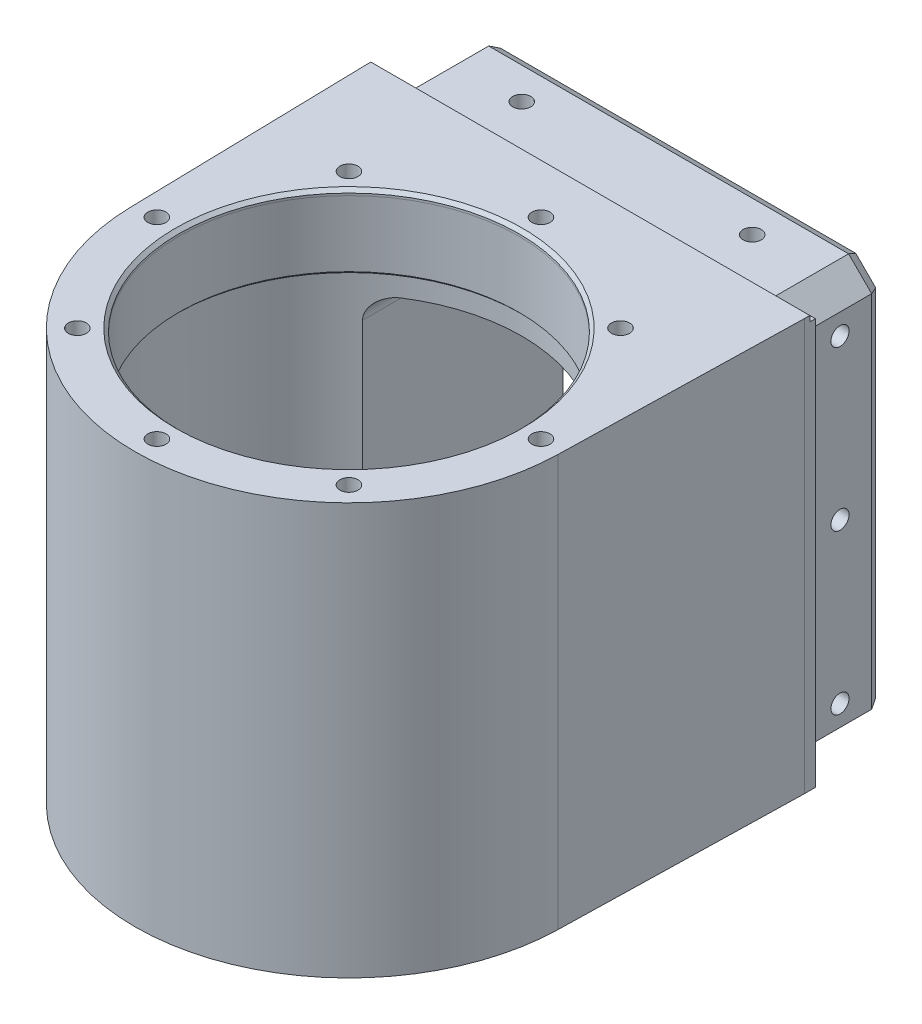
SolidWorks part; units mm, degrees
material "3.3547 (EN-AW 5083)"
ref_plane "Front Plane" through (0, 0, 0) normal (0, 0, 1) x (1, 0, 0)
ref_plane "Top Plane" through (0, 0, 0) normal (0, 1, 0) x (1, 0, 0)
ref_plane "Right Plane" through (0, 0, 0) normal (1, 0, 0) x (0, 0, -1)
ref_axis "Elbow" through (0, -41, 45) along (0, 1, 0)
sketch "Sketch1" plane through (0, 0, 0) normal (1, 0, 0) x (0, 0, -1)
  line L0 (-14, 37) -> (-76, 37) construction
  line L1 (-14, 25) -> (-76, 25) construction
  line L2 (-14, 37) -> (-76, 37) construction
  line L3 (-14, -34) -> (-16, -34)
  line L5 (-76, -34) -> (-14, -34) construction
  line L6 (-76, -34) -> (-14, -34) construction
  line L7 (-16, -34) -> (-16, -37)
  line L8 (-16, -37) -> (-6, -37)
  line L9 (-6, -37) -> (-6, 38)
  line L10 (-6, 38) -> (-14, 38)
  line L11 (-45, 37) -> (-45, -49.5069) construction
  line L12 (-76, -22) -> (-14, -22) construction
  line L13 (-76, -22) -> (-14, -22) construction
  line L14 (-14, 25) -> (-76, 25) construction
  line L15 (-14, 38) -> (-14, 25)
  line L16 (-14, 25) -> (-13.5, 25)
  line L17 (-13.5, 25) -> (-13.5, -22)
  line L18 (-13.5, -22) -> (-14, -22)
  line L19 (-14, -22) -> (-14, -34)
  dimension "D1" = 3
  dimension "D2" = 8
  dimension "D3" = 1
  dimension "D4" = 2
  dimension "D5" = 0.5
revolve "Revolve1" add sketch "Sketch1" angle 360 about axis through (0, -41, 45) along (0, 1, 0)
sketch "Sketch2" plane through (0, 0, 0) normal (1, 0, 0) x (0, 0, -1)
  line L0 (-14, 37) -> (-76, 37) construction
  line L1 (-14, 37) -> (-76, 37) construction
  line L2 (-14, 37) -> (-16, 37)
  line L3 (-16, 37) -> (-16, 41.5)
  line L4 (-16, 41.5) -> (-6, 41.5)
  line L5 (-6, 41.5) -> (-6, 38.5)
  line L6 (-6, 38.5) -> (-14, 38.5)
  line L7 (-14, 38.5) -> (-14, 37)
  line L9 (-45, 37) -> (-45, 58.1094) construction
  line L10 (-6, -37) -> (-6, 38) construction
  line L11 (-6, 38) -> (-84, 38) construction
  dimension "D1" = 2
  dimension "D2" = 3
  dimension "D3" = 0.5
revolve "Revolve2" add sketch "Sketch2" angle 360 about axis through (0, -41, 45) along (0, 1, 0)
sketch "Sketch3" plane through (0, 0, 0) normal (0, 1, 0) x (1, 0, 0)
  line L0 (0, -41.25) -> (0, 41.25) construction
  line L2 (-40, -2) -> (-38.9897, -45.8974)
  line L4 (40, 0) -> (-40, 0) construction
  line L5 (40, 0) -> (-40, 0) construction
  line L6 (40, -2) -> (38.9897, -45.8974)
  line L7 (-40, -2) -> (-40, 0)
  line L8 (40, -2) -> (40, 0)
  line L9 (-40, 0) -> (40, 0)
  circle A0 centre (0, -45) radius 39 construction
  arc A1 (-38.9897, -45.8974) -> (38.9897, -45.8974) centre (0, -45) cw
  point P15 (0, 0)
  dimension "D1" = 2
extrude "Boss-Extrude1" add sketch "Sketch3" along normal up to surface and the other way up to surface contours L2 A1 L6 L8 L9 L7 up to face at (0, 38, 14) other way up to face at (0, -37, 6)
sketch "Sketch4" plane through (0, 0, 0) normal (0, 0, -1) x (-1, 0, 0)
  line L0 (-37, 37) -> (37, 37) construction
  line L1 (-37, 37) -> (37, 37) construction
  line L3 (-37, -37) -> (37, -37)
  line L4 (-37, -37) -> (-37, 37)
  line L5 (-37, 37) -> (37, 37)
  line L6 (37, -37) -> (37, 37)
  line L7 (-37, -37) -> (37, 37) construction
  line L8 (-37, 37) -> (37, -37) construction
  point P2 (0, 0)
extrude "Boss-Extrude2" add sketch "Sketch4" along normal blind 15
sketch "Sketch5" plane through (0, 38, 0) normal (0, 1, 0) x (1, 0, 0)
  line L0 (0, 0) -> (0, -62.5046) construction
  line L1 (-40, 0) -> (40, 0) construction
  line L2 (-29.8132, -10) -> (-29.8132, 0) construction
  line L3 (-29.8132, -10) -> (-39.8106, -10.2301) construction
  line L4 (-40, -2) -> (-38.9897, -45.8974) construction
  circle A1 centre (-29.8132, -10) radius 6
  circle A2 centre (29.8132, -10) radius 6
  dimension "D2" = 12
  dimension "D1" = 10
extrude "Cut-Extrude1" [suppressed] cut sketch "Sketch5" against normal through all
sketch "Sketch12" plane through (0, 41.5, 0) normal (0, 1, 0) x (1, 0, 0)
  line L0 (0, -14) -> (0, -6) construction
  line L1 (0, -45) -> (0, -10) construction
  line L2 (0, -45) -> (24.7487, -20.2513) construction
  circle A2 centre (0, -45) radius 39
  circle A3 centre (0, -45) radius 31 construction
  circle A4 centre (0, -45) radius 39 construction
  circle A6 centre (0, -45) radius 31 construction
  point P11 (0, -10)
  point P20 (24.7487, -20.2513)
  point P21 (35, -45)
  point P22 (24.7487, -69.7487)
  point P23 (0, -80)
  point P24 (-24.7487, -69.7487)
  point P25 (-35, -45)
  point P26 (-24.7487, -20.2513)
  dimension "D1" = 8
  dimension "D2" = 45
hole_wizard "M4 Clearance Hole1" positions "Sketch12" profile "Sketch11" hole size "M4" standard "DIN" end condition up to next
sketch "Sketch11" plane through (-24.7487, 41.5, 20.2513) normal (1, 0, 0) x (0, 0, 1)
  line L0 (0, 0) -> (0, 3)
  line L1 (0, 3) -> (2.15, 3)
  line L2 (2.15, 3) -> (2.15, 0)
  line L5 (2.15, 0) -> (0, 0)
  line L11 (0, -6.35) -> (0, 107.95) construction
  dimension "Thru Hole Dia." = 4.3
  dimension "Thru Hole Depth" = 3
sketch "Sketch17" plane through (0, 38, 0) normal (0, 1, 0) x (1, 0, 0)
  point P0 (0, -10)
  point P3 (24.7487, -20.2513)
  point P6 (35, -45)
  point P9 (-24.7487, -20.2513)
  point P12 (-35, -45)
  point P15 (-24.7487, -69.7487)
  point P18 (0, -80)
  point P21 (24.7487, -69.7487)
hole_wizard "M4 Tapped Hole1" positions "Sketch17" profile "Sketch16" tap size "M4" standard "DIN"
sketch "Sketch16" plane through (0, 38, 10) normal (1, 0, 0) x (0, 0, 1)
  line L0 (0, 0) -> (0, 12.4914)
  line L1 (0, 12.4914) -> (1.65, 11.5)
  line L2 (1.65, 11.5) -> (1.65, 0)
  line L5 (1.65, 0) -> (0, 0)
  line L10 (0, 12.4914) -> (-1.65, 11.5) construction
  line L11 (0, -6.35) -> (0, 107.95) construction
  dimension "Tap Drill Dia." = 3.3
  dimension "Tap Drill Depth" = 11.5
  dimension "Drill Angle" = 118
cosmetic thread "Hole Thread25" parameters "D1"=8, "D2"=4
cosmetic thread "Hole Thread26" parameters "D1"=8, "D2"=4
cosmetic thread "Hole Thread27" parameters "D1"=8, "D2"=4
cosmetic thread "Hole Thread28" parameters "D1"=8, "D2"=4
cosmetic thread "Hole Thread29" parameters "D1"=8, "D2"=4
cosmetic thread "Hole Thread30" parameters "D1"=8, "D2"=4
cosmetic thread "Hole Thread31" parameters "D1"=8, "D2"=4
cosmetic thread "Hole Thread32" parameters "D1"=8, "D2"=4
sketch "Sketch18" plane through (0, 0, 0) normal (1, 0, 0) x (0, 0, -1)
  line L0 (0, 0) -> (-96.5587, 0) construction
  line L1 (-84, 25) -> (-76, 25)
  line L2 (-84, 38) -> (-84, -37) construction
  line L3 (-70.3666, 23.2623) -> (-48.3666, 8.2623)
  line L4 (-84, 25) -> (-84, -22)
  line L5 (-65.9666, -20.2623) -> (-48.3666, -8.2623)
  line L6 (-84, -22) -> (-71.6, -22)
  line L7 (-45.8974, 38) -> (-84, 38) construction
  line L8 (-84, -37) -> (-45.8974, -37) construction
  arc A0 (-65.9666, -20.2623) -> (-71.6, -22) centre (-71.6, -12) cw
  arc A1 (-48.3666, 8.2623) -> (-48.3666, -8.2623) centre (-54, 0) cw
  arc A2 (-76, 25) -> (-70.3666, 23.2623) centre (-76, 15) cw
  point P10 (-77, 0)
  point P13 (-68.5153, -22)
  point P16 (-36.2486, 0)
  point P19 (-72.9153, 25)
  point P22 (-77.8, -22)
  dimension "D1" = 10
  dimension "D2" = 13
  dimension "D3" = 30
  dimension "D4" = 8
  dimension "D5" = 15
  dimension "D6" = 12.4
extrude "Cut-Extrude2" [suppressed] cut sketch "Sketch18" against normal through all both and the other way through all
sketch "Sketch19" plane through (0, 0, 0) normal (0, 0, -1) x (-1, 0, 0)
  line L1 (40, -37) -> (37, -37)
  line L2 (40, -37) -> (40, 38)
  line L6 (37, 37) -> (-37, 37) construction
  line L7 (37, 37) -> (-37, 37)
  line L8 (37, -37) -> (37, 37) construction
  line L9 (37, -37) -> (37, 37)
  line L11 (40, 38) -> (-40, 38) construction
  line L12 (40, 38) -> (-40, 38)
  line L13 (-40, 38) -> (-40, 37)
  line L14 (-40, 38) -> (-40, -37) construction
  line L15 (-40, 37) -> (-37, 37)
extrude "Cut-Extrude3" cut sketch "Sketch19" against normal blind 1
sketch "Sketch20" plane through (0, 0, 0) normal (1, 0, 0) x (0, 0, -1)
  line L0 (-14, 37) -> (-76, 37) construction
  line L1 (-14, 37) -> (-76, 37)
split line "Split Line1"
other "Move Face1" [suppressed] parameters "D1"=0.55
hole_wizard "M4 Tapped Hole2" positions "3DSketch2" profile "Sketch9" tap size "M4" standard "DIN"
sketch3d "3DSketch2"
  line L0 (37, 37, -7.5) -> (37, 29, -7.5) construction
  line L1 (37, 37, -15) -> (37, 37, 0) construction
  line L2 (37, 29, -7.5) -> (37, -29, -7.5) construction
  line L3 (37, 37, -7.5) -> (-37, 37, -7.5) construction
  line L4 (-37, 37, -15) -> (-37, 37, 1) construction
  point P0 (37, 29, -7.5)
  point P10 (37, -29, -7.5)
  point P12 (-37, -29, -7.5)
  point P13 (-37, 29, -7.5)
  point P18 (37, 0, -7.5)
  point P21 (37, 0, -7.5)
  point P23 (-37, 0, -7.5)
  point P29 (21, 37, -7.5)
  point P33 (-21, 37, -7.5)
  point P35 (-21, -37, -7.5)
  point P36 (21, -37, -7.5)
  dimension "D2" = 16
  dimension "D1" = 8
sketch "Sketch9" plane through (37, 29, -7.5) normal (0, 1, 0) x (0, 0, -1)
  line L0 (0, 0) -> (0, 11.0914)
  line L1 (0, 11.0914) -> (1.65, 10.1)
  line L2 (1.65, 10.1) -> (1.65, 0)
  line L5 (1.65, 0) -> (0, 0)
  line L10 (0, 11.0914) -> (-1.65, 10.1) construction
  line L11 (0, -6.35) -> (0, 107.95) construction
  dimension "Tap Drill Dia." = 3.3
  dimension "Tap Drill Depth" = 10.1
  dimension "Drill Angle" = 118
cosmetic thread "Hole Thread33" parameters "D1"=8, "D2"=4
cosmetic thread "Hole Thread34" parameters "D1"=8, "D2"=4
cosmetic thread "Hole Thread35" parameters "D1"=8, "D2"=4
cosmetic thread "Hole Thread36" parameters "D1"=8, "D2"=4
cosmetic thread "Hole Thread37" parameters "D1"=8, "D2"=4
cosmetic thread "Hole Thread38" parameters "D1"=8, "D2"=4
cosmetic thread "Hole Thread39" parameters "D1"=8, "D2"=4
cosmetic thread "Hole Thread40" parameters "D1"=8, "D2"=4
cosmetic thread "Hole Thread41" parameters "D1"=8, "D2"=4
cosmetic thread "Hole Thread42" parameters "D1"=8, "D2"=4
chamfer "Chamfer1" distance 4.2 angle 45 4 edges at (-37, 37, -7) (-37, -37, -7) (37, -37, -7.5) (37, 37, -7.5)
chamfer "Chamfer2" distance 1 angle 60 8 edges at (-34.9, -34.9, -15) (0, -37, -15) (34.9, -34.9, -15) (37, 0, -15) (34.9, 34.9, -15) (0, 37, -15) (-34.9, 34.9, -15) (-37, 0, -15)
fillet "Fillet1" radius 0.3 1 edges at (0, -34, 14)
chamfer "Chamfer3" distance 0.6 angle 45 1 edges at (0, 38, 14)
chamfer "Chamfer4" distance 0.5 angle 45 2 edges at (0, 25, 13.5) (0, -22, 13.5)
fillet "Fillet2" radius 0.4 1 edges at (0, 38.5, 14)
sketch "Sketch21" plane through (0, 0, -15) normal (0, 0, -1) x (-1, 0, 0)
  line L16 (-21, -21) -> (21, -21)
  line L17 (21, -21) -> (21, 21)
  line L18 (21, 21) -> (-21, 21)
  line L19 (-21, 21) -> (-21, -21)
  line L20 (-17, -21) -> (17, -21)
  line L21 (21, -17) -> (21, 17)
  line L22 (17, 21) -> (-17, 21)
  line L23 (-21, 17) -> (-21, -17)
  arc A0 (-17, -21) -> (-21, -17) centre (-17, -17) cw
  arc A1 (17, -21) -> (21, -17) centre (17, -17) ccw
  arc A2 (21, 17) -> (17, 21) centre (17, 17) ccw
  arc A3 (-17, 21) -> (-21, 17) centre (-17, 17) ccw
  dimension "D2" = 4
  dimension "D1" = 15
extrude "Cut-Extrude4" cut sketch "Sketch21" against normal up to next
delete or keep bodies "Body-Delete/Keep 1" type delete bodies bodies 109
delete or keep bodies "Body-Delete/Keep 2" [suppressed] type delete bodies bodies 118
equation "\"D2@3DSketch2\"=\"D1@3DSketch2\"*2"
